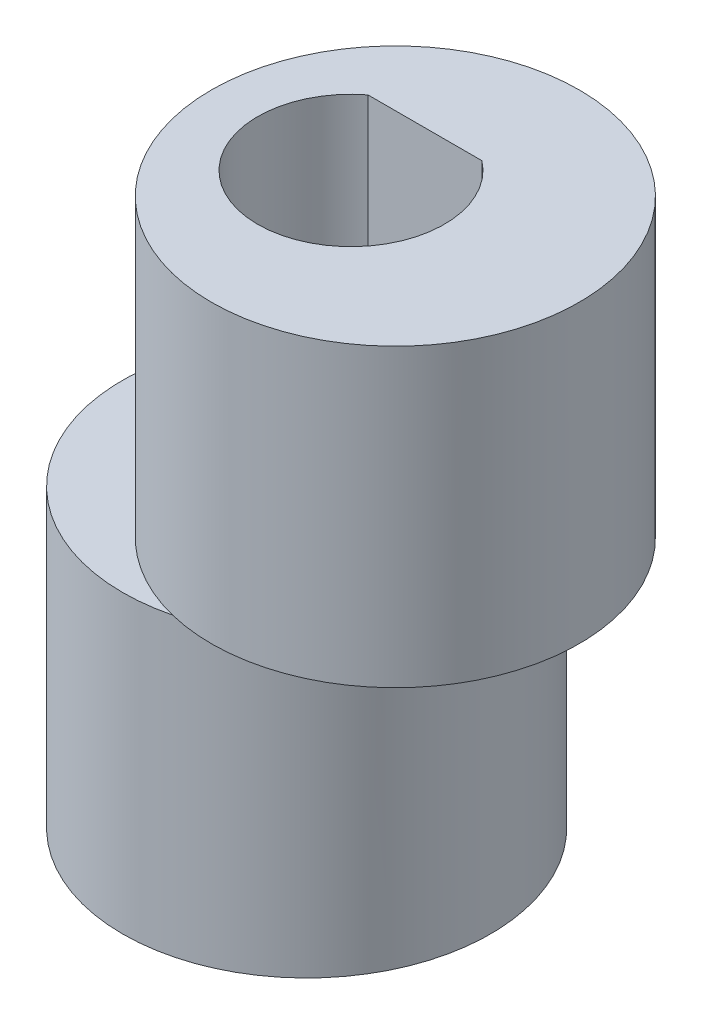
SolidWorks part; units mm, degrees
ref_plane "Front Plane" through (0, 0, 0) normal (0, 0, 1) x (1, 0, 0)
ref_plane "Top Plane" through (0, 0, 0) normal (0, 1, 0) x (1, 0, 0)
ref_plane "Right Plane" through (0, 0, 0) normal (1, 0, 0) x (0, 0, -1)
sketch "Sketch1" plane through (0, 0, 0) normal (0, 1, 0) x (1, 0, 0)
  line L0 (0, 0) -> (-2.4, 0)
  circle A0 centre (0, 0) radius 4.975
  circle A1 centre (-2.4, 0) radius 4.975
  circle A2 centre (-1.2, 0) radius 2.525
  dimension "D1" = 9.95
  dimension "D2" = 9.95
  dimension "D3" = 5.05
extrude "Boss-Extrude1" add sketch "Sketch1" along normal blind 8 contours A2 | A0 A1 A2 | A1 A0 region at (2.746, 0, 0) region at (1.4227, 0, -2.9889) region at (-3.6536, 0, 0)
sketch "Sketch2" plane through (0, 0, 0) normal (0, 1, 0) x (1, 0, 0)
  circle A0 centre (-2.4, 0) radius 4.975
extrude "Boss-Extrude2" add sketch "Sketch2" against normal blind 8
extrude "Cut-Extrude1" cut sketch "Sketch1<4>" against normal blind 8 and the other way blind 8 contours A2
sketch "Sketch1<4>" plane through (0, 0, 0) normal (0, 1, 0) x (1, 0, 0) same geometry as "Sketch1"
sketch "Sketch3" plane through (0, 8, 0) normal (0, 1, 0) x (1, 0, 0)
  line L1 (0.3413, 2) -> (-2.7413, 2)
  circle A0 centre (-1.2, 0) radius 2.525 construction
  arc A1 (-2.7413, 2) -> (0.3413, 2) centre (-1.2, 0) cw
  circle M3 centre (-1.2, 0) radius 2.525
extrude "Boss-Extrude3" add sketch "Sketch3" against normal blind 10 contours L1 M3 region at (-1.2, 8, -2.212)
